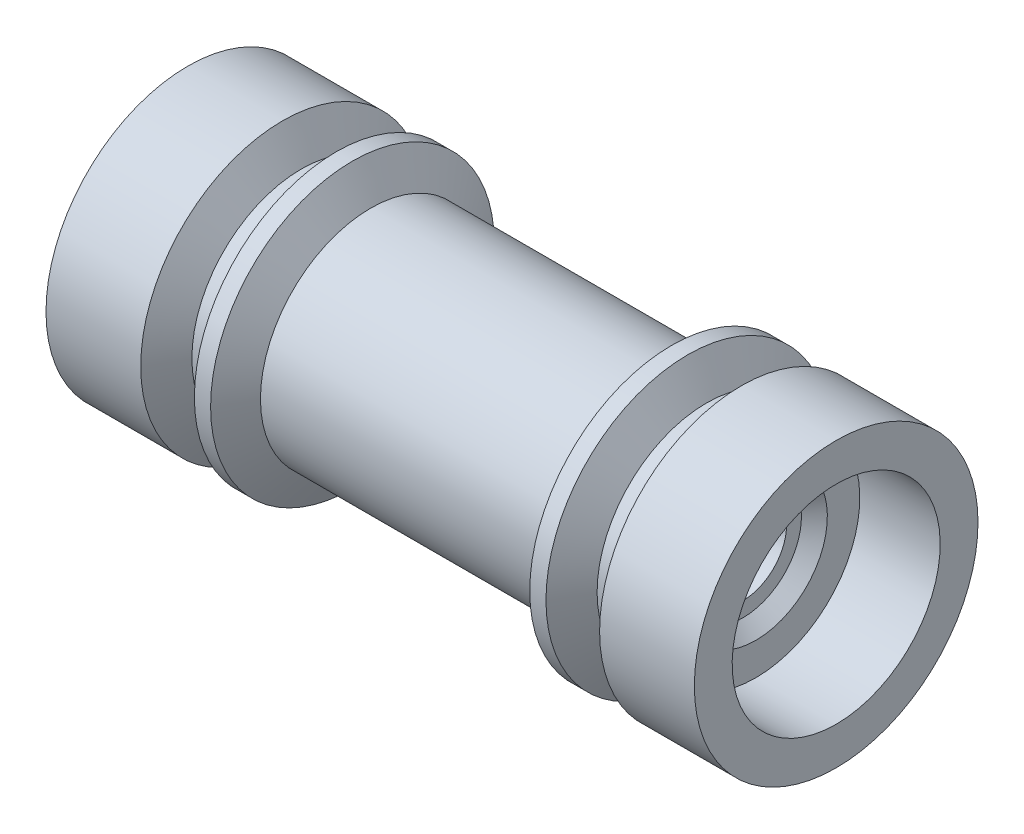
SolidWorks part; units mm, degrees
ref_plane "Front Plane" through (0, 0, 0) normal (0, 0, 1) x (1, 0, 0)
ref_plane "Top Plane" through (0, 0, 0) normal (0, 1, 0) x (1, 0, 0)
ref_plane "Right Plane" through (0, 0, 0) normal (1, 0, 0) x (0, 0, -1)
sketch "Sketch2" plane through (0, 0, 0) normal (0, 0, 1) x (1, 0, 0)
  line L0 (0, 0) -> (0, 28.4375) construction
  line L1 (-12.7, 4.075) -> (-9.55, 4.075) construction
  line L2 (-12.7, 4.075) -> (-12.7, -4.075) construction
  line L3 (-12.7, -4.075) -> (-9.55, -4.075) construction
  line L4 (-9.55, 4.075) -> (-9.55, -4.075) construction
  line L5 (-12.7, 4.075) -> (-9.55, -4.075) construction
  line L6 (-12.7, -4.075) -> (-9.55, 4.075) construction
  line L7 (9.55, 4.5) -> (54.0332, 4.5) construction
  line L8 (9.55, 4.5) -> (9.55, -4.5) construction
  line L9 (9.55, -4.5) -> (54.0332, -4.5) construction
  line L10 (54.0332, 4.5) -> (54.0332, -4.5) construction
  line L11 (9.55, 4.5) -> (54.0332, -4.5) construction
  line L12 (9.55, -4.5) -> (54.0332, 4.5) construction
  line L13 (-12.7, 0) -> (54.0332, 0) construction
  line L14 (-12.7, 5.5562) -> (-8.9882, 5.5562)
  line L21 (-5.5369, 4.318) -> (0, 4.318)
  line L22 (-12.7, 5.5562) -> (-12.7, 4.075)
  line L23 (-12.7, 4.075) -> (-9.55, 4.075)
  line L24 (-9.55, 4.075) -> (-9.55, 0)
  line L25 (-9.55, 0) -> (0, 0)
  line L26 (0, 0) -> (0, 4.318)
  line L27 (-33.5594, -5.5562) -> (-33.5594, 5.5562) construction
  line L28 (-8.9882, 5.5562) -> (-8.255, 4.2862)
  line L29 (-8.255, 4.2862) -> (-7.62, 4.2862)
  line L30 (-12.7, 5.5562) -> (12.7, 5.5562) construction
  line L31 (0, 1.6) -> (-12.5, 1.6)
  line L32 (-12.5, 1.6) -> (-14.1, 0)
  line L33 (-12.5, 1.6) -> (-12.5, -1.6) construction
  line L34 (-12.5, 1.6) -> (12.5, 1.6) construction
  line L35 (-9.55, 1.7145) -> (-2.875, 1.7145)
  line L36 (-2.875, 1.7145) -> (-2.875, 0)
  line L37 (-9.55, 2.805) -> (-9.042, 2.297)
  line L38 (-2.875, 1.7145) -> (-15.875, 1.7145) construction
  line L39 (-2.875, 1.7145) -> (-2.875, -1.7145) construction
  line L40 (-2.875, -1.7145) -> (-15.875, -1.7145) construction
  line L41 (-15.875, 1.7145) -> (-15.875, -1.7145) construction
  line L42 (-9.042, 2.297) -> (-9.042, 0)
  line L46 (-7.62, 4.2862) -> (-6.8868, 5.5562)
  line L47 (-6.8868, 5.5562) -> (-6.2518, 5.5562)
  line L48 (-6.2518, 5.5562) -> (-5.5369, 4.318)
  line L49 (-7.9375, 4.2862) -> (-7.9375, 6.3987) construction
  line L50 (-7.9375, 6.3987) -> (7.9375, 6.3987) construction
  point P0 (-11.125, 0)
  point P5 (31.7916, 0)
  point P27 (-33.5594, 0)
  point P29 (-12.5, 0)
  point P33 (0, 6.3987)
  point P36 (0, 1.6)
  point P48 (-2.875, 0)
  point P51 (0, 5.5562)
  dimension "D3" = 4.318
  dimension "D4" = 11.1125
  dimension "D5" = 8.15
  dimension "D6" = 60
  dimension "D7" = 0.635
  dimension "D8" = 60
  dimension "D9" = 15.875
  dimension "D10" = 1.27
  dimension "D11" = 25.4
  dimension "D12" = 0.635
  dimension "D13" = 45
  dimension "D14" = 25
  dimension "D15" = 3.2
  dimension "D16" = 3.429
  dimension "D17" = 3.175
  dimension "D18" = 1.27
  dimension "D19" = 0.508
  dimension "D20" = 45
  dimension "D21" = 13
  dimension "D22" = 3.15
revolve "Revolve1" add sketch "Sketch2" angle 360 about L13 region at (-5.8431, 3.4326, 0)
mirror "Mirror1" about plane through (0, 0, 0) normal (1, 0, 0) of bodies 101
chamfer "Chamfer1" distance 0.508 angle 45 1 edges at (-12.7, -4.075, 0)
